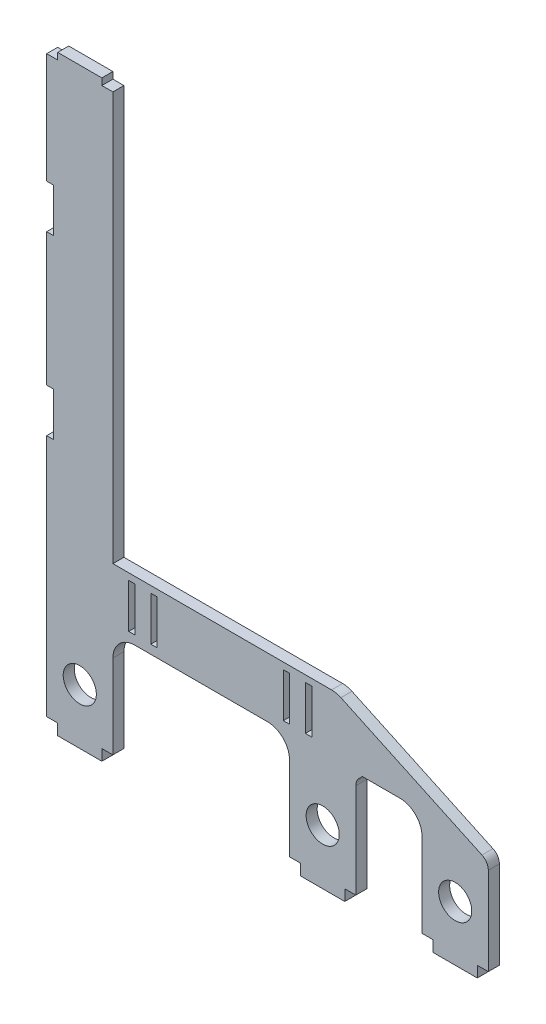
SolidWorks part; units mm, degrees
ref_plane "Front Plane" through (0, 0, 0) normal (0, 0, 1) x (1, 0, 0)
ref_plane "Top Plane" through (0, 0, 0) normal (0, 1, 0) x (1, 0, 0)
ref_plane "Right Plane" through (0, 0, 0) normal (1, 0, 0) x (0, 0, -1)
sketch "Sketch1" plane through (0, 0, 0) normal (0, 0, 1) x (1, 0, 0)
  line L0 (38.6, 72) -> (38.6, 52) construction
  line L1 (48.6, 72) -> (48.6, 52) construction
  line L2 (108.6, 72) -> (108.6, 52) construction
  line L3 (118.6, 72) -> (118.6, 52) construction
  line L4 (155, 62.0711) -> (155, 65.5389)
  line L5 (150.5677, 70.5065) -> (34.4323, 83.7792)
  line L6 (30, 88.7468) -> (30, 260)
  line L7 (30, 260) -> (25, 260)
  line L8 (25, 260) -> (25, 263)
  line L9 (25, 263) -> (5, 263)
  line L10 (5, 263) -> (5, 260)
  line L11 (5, 260) -> (0, 260)
  line L12 (0, 260) -> (0, 0)
  line L13 (0, 0) -> (5, 0)
  line L14 (5, 0) -> (5, -5)
  line L15 (5, -5) -> (25, -5)
  line L16 (25, -5) -> (25, 0)
  line L17 (25, 0) -> (30, 0)
  line L18 (30, 0) -> (30, 40)
  line L19 (35, 45) -> (105, 45)
  line L20 (110, 40) -> (110, 0)
  line L21 (110, 0) -> (115, 0)
  line L22 (115, 0) -> (115, -5)
  line L23 (115, -5) -> (135, -5)
  line L24 (135, -5) -> (135, 0)
  line L25 (135, 0) -> (140, 0)
  line L26 (140, 0) -> (140, 42.9289)
  line L27 (141.4645, 46.4645) -> (153.5355, 58.5355)
  line L28 (40.05, 52) -> (37.15, 52)
  line L29 (40.05, 72) -> (40.05, 52)
  line L30 (37.15, 52) -> (37.15, 72)
  line L31 (37.15, 72) -> (40.05, 72)
  line L32 (47.15, 72) -> (50.05, 72)
  line L33 (47.15, 52) -> (47.15, 72)
  line L34 (50.05, 72) -> (50.05, 52)
  line L35 (50.05, 52) -> (47.15, 52)
  line L36 (117.15, 72) -> (120.05, 72)
  line L37 (120.05, 72) -> (120.05, 52)
  line L38 (120.05, 52) -> (117.15, 52)
  line L39 (117.15, 52) -> (117.15, 72)
  line L40 (110.05, 52) -> (107.15, 52)
  line L41 (110.05, 72) -> (110.05, 52)
  line L42 (107.15, 52) -> (107.15, 72)
  line L43 (107.15, 72) -> (110.05, 72)
  arc A0 (155, 65.5389) -> (150.5677, 70.5065) centre (150, 65.5389) ccw
  arc A1 (30, 88.7468) -> (34.4323, 83.7792) centre (35, 88.7468) ccw
  arc A2 (35, 45) -> (30, 40) centre (35, 40) ccw
  arc A3 (110, 40) -> (105, 45) centre (105, 40) ccw
  arc A4 (141.4645, 46.4645) -> (140, 42.9289) centre (145, 42.9289) ccw
  arc A5 (153.5355, 58.5355) -> (155, 62.0711) centre (150, 62.0711) ccw
  dimension "D20" = 260
  dimension "D21" = 5
  dimension "D23" = 5
  dimension "D24" = 5
  dimension "D25" = 5
  dimension "D26" = 5
  dimension "D27" = 5
  dimension "D1" = 20
  dimension "D2" = 5
  dimension "D3" = 5
  dimension "D4" = 30
  dimension "D5" = 38.6
  dimension "D6" = 10
  dimension "D7" = 110
  dimension "D8" = 5
  dimension "D9" = 20
  dimension "D10" = 30
  dimension "D11" = 108.6
  dimension "D12" = 10
  dimension "D13" = 155
  dimension "D14" = 45
  dimension "D15" = 7
  dimension "D16" = 20
  dimension "D17" = 2.9
  dimension "D18" = 2.9
  dimension "D19" = 6.52
  dimension "D22" = 135
  dimension "D28" = 42.9289
  dimension "D29" = 3.4678
  dimension "D30" = 20
  dimension "D31" = 5
  dimension "D32" = 3
  dimension "D33" = 2.9
  dimension "D34" = 2.9
extrude "Boss-Extrude1" add sketch "Sketch1" along normal blind 5
sketch "Sketch2" plane through (0, 0, 5) normal (0, 0, 1) x (1, 0, 0)
  line L0 (30, 40) -> (30, 48)
  line L1 (30, 48) -> (110, 48)
  line L2 (110, 48) -> (110, 40)
  line L3 (35, 45) -> (105, 45) construction
  line L4 (35, 45) -> (105, 45)
  arc A0 (35, 45) -> (30, 40) centre (35, 40) ccw construction
  arc A1 (110, 40) -> (105, 45) centre (105, 40) ccw construction
  arc A2 (35, 45) -> (30, 40) centre (35, 40) ccw
  arc A3 (110, 40) -> (105, 45) centre (105, 40) ccw
  dimension "D1" = 3
extrude "Cut-Extrude1" cut sketch "Sketch2" against normal through all
fillet "Fillet1" radius 10 2 edges at (30, 48, 2.5) (110, 48, 2.5)
sketch "Sketch3" plane through (0, 0, 0) normal (0, 0, -1) x (-1, 0, 0)
  line L0 (0, 260) -> (0, 0) construction
  line L1 (0, 210) -> (-3, 210)
  line L2 (0, 210) -> (0, 190.2)
  line L3 (0, 190.2) -> (-3, 190.2)
  line L4 (-3, 210) -> (-3, 190.2)
  line L6 (-5, 260) -> (0, 260) construction
  dimension "D1" = 3
  dimension "D2" = 19.8
  dimension "D3" = 50
extrude "Cut-Extrude2" cut sketch "Sketch3" against normal blind 5
pattern_linear "LPattern1" count 2 spacing 80 along (0, -1, 0) of "Cut-Extrude2"
sketch "Sketch4" plane through (0, 0, 5) normal (0, 0, 1) x (1, 0, 0)
  line L0 (30, 88.7468) -> (30, 75)
  line L1 (30, 75) -> (111.25, 75)
  line L2 (150.5677, 70.5065) -> (34.4323, 83.7792) construction
  line L3 (111.25, 75) -> (34.4323, 83.7792)
  line L5 (50.05, 72) -> (47.15, 72) construction
  arc A0 (30, 88.7468) -> (34.4323, 83.7792) centre (35, 88.7468) ccw construction
  arc A1 (30, 88.7468) -> (34.4323, 83.7792) centre (35, 88.7468) ccw
  dimension "D1" = 3
extrude "Cut-Extrude3" cut sketch "Sketch4" against normal blind 10
sketch "Sketch5" plane through (0, 0, 5) normal (0, 0, 1) x (1, 0, 0)
  line L0 (111.25, 75) -> (131.25, 75)
  line L1 (131.25, 75) -> (153.5355, 58.5355)
  line L2 (141.4645, 46.4645) -> (153.5355, 58.5355) construction
  line L3 (111.25, 75) -> (134.91, 72.296)
  line L4 (150.5677, 70.5065) -> (111.25, 75) construction
  line L5 (155, 62.0711) -> (155, 65.5389) construction
  line L6 (150.5677, 70.5065) -> (111.25, 75)
  line L7 (155, 62.0711) -> (155, 65.5389)
  arc A0 (155, 65.5389) -> (150.5677, 70.5065) centre (150, 65.5389) ccw construction
  arc A1 (153.5355, 58.5355) -> (155, 62.0711) centre (150, 62.0711) ccw construction
  arc A2 (155, 65.5389) -> (150.5677, 70.5065) centre (150, 65.5389) ccw
  arc A3 (153.5355, 58.5355) -> (155, 62.0711) centre (150, 62.0711) ccw
  dimension "D1" = 20
extrude "Cut-Extrude4" cut sketch "Sketch5" against normal blind 5 contours L1 A3 L7 A2 L6 region at (147.9818, 66.6486, 5)
extrude "Boss-Extrude2" add sketch "Sketch5<3>" against normal blind 5 contours L0 L3 L1 region at (125.8033, 74.0987, 5)
sketch "Sketch5<3>" plane through (0, 0, 5) normal (0, 0, 1) x (1, 0, 0) same geometry as "Sketch5"
sketch "Sketch10" plane through (0, 0, 0) normal (0, 0, -1) x (-1, 0, 0)
  line L0 (-131.25, 75) -> (-200, 42.9413)
  line L1 (-200, 42.9413) -> (-200, 0)
  line L2 (-200, 0) -> (-170, 0)
  line L4 (-170, 0) -> (-170, 48)
  line L6 (-170, 48) -> (-143, 48)
  line L7 (-141.4645, 46.4645) -> (-153.5355, 58.5355) construction
  line L8 (-30, 75) -> (-131.25, 75) construction
  line L10 (-30, 0) -> (-30, 38) construction
  line L11 (-143, 48) -> (-153.5355, 58.5355)
  line L12 (-153.5355, 58.5355) -> (-131.25, 75)
  line L13 (-100, 48) -> (-40, 48) construction
  line L15 (-25, 0) -> (-30, 0) construction
  dimension "D1" = 25
  dimension "D2" = 30
  dimension "D3" = 170
extrude "Boss-Extrude3" add sketch "Sketch10" against normal up to vertex (5 mm away) up to point (153.5355, 58.5355, 5)
fillet "Fillet3" radius 10 2 edges at (131.25, 75, 2.5) (170, 48, 2.5)
fillet "Fillet4" radius 5 1 edges at (200, 42.9413, 2.5)
sketch "Sketch12" plane through (0, 0, 5) normal (0, 0, 1) x (1, 0, 0)
  line L0 (200, 0) -> (170, 0) construction
  line L1 (175, 0) -> (195, 0)
  line L2 (175, 0) -> (175, -5)
  line L3 (175, -5) -> (195, -5)
  line L4 (195, 0) -> (195, -5)
  line L5 (170, 0) -> (170, 38) construction
  dimension "D1" = 5
  dimension "D2" = 20
  dimension "D3" = 5
extrude "Boss-Extrude4" add sketch "Sketch12" against normal up to vertex (5 mm away) up to point (200, 0, 0)
sketch "Sketch13" plane through (0, 0, 5) normal (0, 0, 1) x (1, 0, 0)
  line L0 (5, -5) -> (25, -5) construction
  line L1 (0, 110.2) -> (0, 0) construction
  line L2 (110, 38) -> (110, 0) construction
  line L3 (170, 0) -> (170, 38) construction
  circle A0 centre (15, 20) radius 7.5
  circle A1 centre (125, 20) radius 7.5
  circle A2 centre (185, 20) radius 7.5
  dimension "D1" = 15
  dimension "D2" = 25
  dimension "D3" = 15
  dimension "D4" = 15
  dimension "D5" = 15
extrude "Cut-Extrude6" cut sketch "Sketch13" against normal through all
